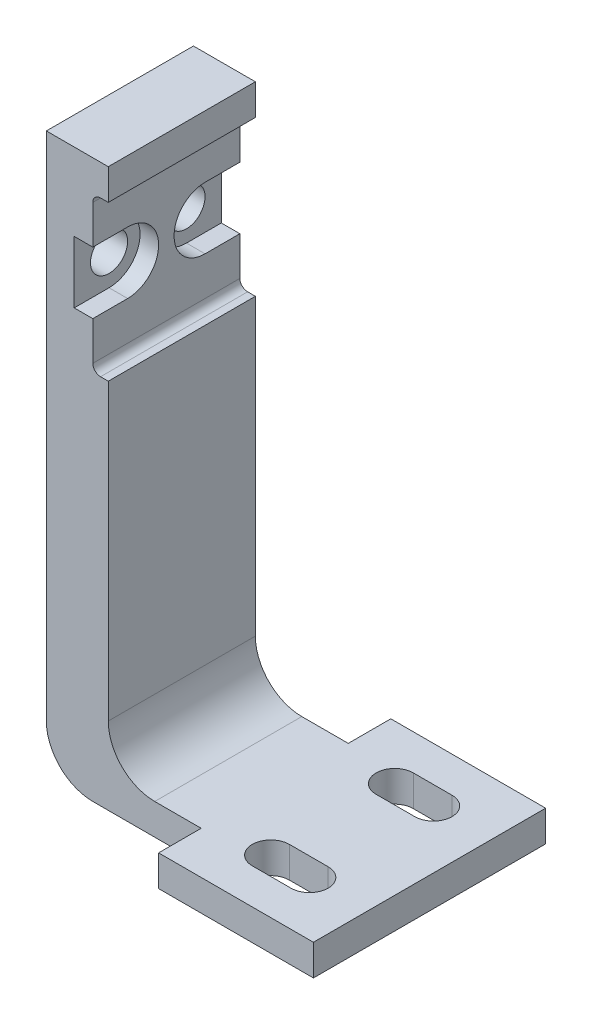
SolidWorks part; units mm, degrees
material "6061-T6 (SS)"
ref_plane "Front Plane" through (0, 0, 0) normal (0, 0, 1) x (1, 0, 0)
ref_plane "Top Plane" through (0, 0, 0) normal (0, 1, 0) x (1, 0, 0)
ref_plane "Right Plane" through (0, 0, 0) normal (1, 0, 0) x (0, 0, -1)
sketch "Sketch1" plane through (0, 0, 0) normal (0, 0, 1) x (1, 0, 0)
  line L0 (-14.4886, 20.9) -> (-16.5374, 20.9) construction
  line L9 (-16.5374, 15.9) -> (-16.5374, 25.9)
  line L10 (-19.5374, 0) -> (-19.5374, 27.9)
  line L11 (-19.5374, 27.9) -> (-15.5374, 27.9)
  line L12 (-15.5374, 27.9) -> (-15.5374, 25.9)
  line L17 (-15.4274, -6.11) -> (0.4626, -6.11)
  line L18 (0.4626, -6.11) -> (0.4626, -8.11)
  line L19 (0.4626, -8.11) -> (-11.4274, -8.11)
  line L20 (-16.5374, 25.9) -> (-15.5374, 25.9)
  line L21 (-16.5374, 15.9) -> (-15.5374, 15.9)
  line L22 (-15.5374, 15.9) -> (-15.5374, 12.9)
  line L23 (-19.5374, 0) -> (-19.5374, -8.11)
  line L24 (-19.5374, -8.11) -> (-11.4274, -8.11)
  line L25 (-15.5374, 12.9) -> (-15.5374, -6.11)
  line L26 (-15.5374, -6.11) -> (-15.4274, -6.11)
  line L29 (-15.4274, -6.11) -> (-13.0144, -6.11) construction
  point P15 (-16.5374, 20.9)
  point P21 (-12.4274, 0)
  dimension "D3" = 36.01
  dimension "D4" = 3
  dimension "D2" = 4
  dimension "D5" = 20
  dimension "D6" = 10
  dimension "D7" = 2
  dimension "D8" = 1
  dimension "D10" = 2
extrude "Boss-Extrude1" add sketch "Sketch1" along normal mid plane 9.5
sketch "Sketch2" plane through (-16.5374, 0, 0) normal (1, 0, 0) x (0, 0, -1)
  line L0 (-4.75, 20.9) -> (4.75, 20.9) construction
  line L1 (-4.75, 15.9) -> (-4.75, 25.9) construction
  line L2 (4.75, 15.9) -> (4.75, 25.9) construction
  point P8 (-2.5, 20.9)
  point P9 (0, 20.9)
  point P11 (2.5, 20.9)
  dimension "D2" = 2.5
  dimension "D1" = 2.5
hole_wizard "M2 Clearance Hole1" positions "3DSketch1" profile "Sketch3" hole size "M2" standard "ANSI Metric" end condition through all
sketch3d "3DSketch1"
  point P0 (-16.5374, 20.9, 2.5)
  point P3 (-16.5374, 20.9, -2.5)
sketch "Sketch3" plane through (-16.5374, 20.9, 2.5) normal (0, 1, 0) x (0, 0, -1)
  line L0 (0, 0) -> (0, 3)
  line L1 (0, 3) -> (1.2, 3)
  line L2 (1.2, 3) -> (1.2, 0)
  line L5 (1.2, 0) -> (0, 0)
  line L11 (0, -6.35) -> (0, 107.95) construction
  dimension "Thru Hole Dia." = 2.4
  dimension "Thru Hole Depth" = 3
sketch "Sketch4" plane through (-16.5374, 0, 0) normal (1, 0, 0) x (0, 0, -1)
  line L0 (-2.5, 22.9) -> (-4.75, 22.9)
  line L1 (-4.75, 15.9) -> (-4.75, 25.9) construction
  line L2 (-4.75, 22.9) -> (-4.75, 18.9)
  line L3 (-4.75, 18.9) -> (-2.5, 18.9)
  line L4 (0, 55) -> (0, -55) construction
  line L5 (4.75, 18.9) -> (2.5, 18.9)
  line L6 (4.75, 22.9) -> (4.75, 18.9)
  line L7 (2.5, 22.9) -> (4.75, 22.9)
  arc A0 (-2.5, 18.9) -> (-2.5, 22.9) centre (-2.5, 20.9) ccw
  arc A1 (2.5, 22.9) -> (2.5, 18.9) centre (2.5, 20.9) ccw
  point P1 (-7.2767, 21.0548)
  dimension "D1" = 4
  dimension "D2" = 4
extrude "Cut-Extrude1" cut sketch "Sketch4" against normal blind 1.2
sketch "Sketch5" plane through (0, -8.11, 0) normal (0, -1, 0) x (1, 0, 0)
  line L0 (0.4626, -7.5) -> (0.4626, 7.5)
  line L1 (0.4626, 4.75) -> (0.4626, -4.75) construction
  line L2 (0.4626, 7.5) -> (-9.5374, 7.5)
  line L3 (-9.5374, 7.5) -> (-9.5374, -7.5)
  line L4 (-9.5374, -7.5) -> (0.4626, -7.5)
  point P3 (0.4626, 0)
  dimension "D1" = 10
  dimension "D2" = 15
extrude "Boss-Extrude2" add sketch "Sketch5" against normal blind 2
sketch "Sketch6" plane through (0, -6.11, 0) normal (0, 1, 0) x (1, 0, 0)
  line L0 (0.4626, 0) -> (-9.5374, 0) construction
  line L1 (0.4626, 7.5) -> (0.4626, -7.5) construction
  line L2 (-3.2874, -4) -> (-5.7874, -4) construction
  line L3 (-4.5374, -7.5) -> (-4.5374, 7.5) construction
  line L4 (0.4626, -7.5) -> (-9.5374, -7.5) construction
  line L5 (-9.5374, 7.5) -> (0.4626, 7.5) construction
  line L6 (-3.2874, -5.2) -> (-5.7874, -5.2)
  line L7 (-3.2874, -2.8) -> (-5.7874, -2.8)
  line L8 (-3.2874, 4) -> (-5.7874, 4) construction
  line L9 (-3.2874, 5.2) -> (-5.7874, 5.2)
  line L10 (-3.2874, 2.8) -> (-5.7874, 2.8)
  arc A0 (-3.2874, -5.2) -> (-3.2874, -2.8) centre (-3.2874, -4) ccw
  arc A1 (-5.7874, -2.8) -> (-5.7874, -5.2) centre (-5.7874, -4) ccw
  arc A2 (-3.2874, 5.2) -> (-3.2874, 2.8) centre (-3.2874, 4) cw
  arc A3 (-5.7874, 2.8) -> (-5.7874, 5.2) centre (-5.7874, 4) cw
  point P12 (-4.5374, -4)
  point P13 (-4.5374, 0)
  point P14 (-4.5374, 4)
  point P15 (-4.5374, -4)
  point P23 (-4.5374, 4)
  dimension "D3" = 1.2
  dimension "D1" = 4
  dimension "D2" = 2.5
extrude "Cut-Extrude2" cut sketch "Sketch6" against normal up to surface (2 mm away) up to face at (-9.5374, -8.11, 0)
fillet "Fillet1" radius 3 2 edges at (-15.5374, -6.11, 0) (-19.5374, -8.11, 0)
fillet "Fillet2" radius 0.5 2 edges at (-16.5374, 15.9, 0) (-16.5374, 25.9, 0)
